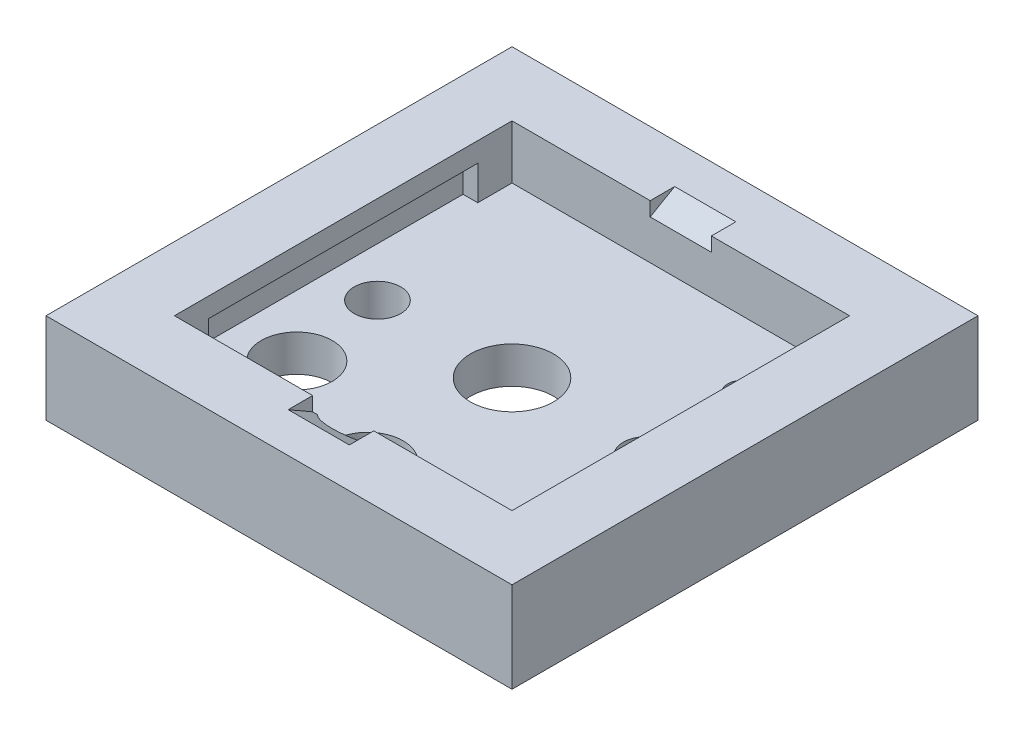
SolidWorks part; units mm, degrees
other "single-1350"
ref_plane "Front Plane" through (0, 0, 0) normal (0, 0, 1) x (1, 0, 0)
ref_plane "Top Plane" through (0, 0, 0) normal (0, 1, 0) x (1, 0, 0)
ref_plane "Right Plane" through (0, 0, 0) normal (1, 0, 0) x (0, 0, -1)
sketch "Sketch1" plane through (0, 0, 0) normal (0, 1, 0) x (1, 0, 0)
  line L0 (-6.9, 6.9) -> (6.9, 6.9)
  line L1 (6.9, 6.9) -> (6.9, -6.9)
  line L2 (6.9, -6.9) -> (1.05, -6.9)
  line L3 (-6.9, -6.9) -> (-6.9, 6.9)
  line L4 (13.0003, 0) -> (-13.0003, 0) construction
  line L5 (0, 13.0493) -> (0, -13.0493) construction
  line L6 (-1.05, -6.9) -> (-6.9, -6.9)
  line L8 (-9.525, -9.525) -> (9.525, -9.525)
  line L9 (-9.525, -9.525) -> (-9.525, 9.525)
  line L10 (-9.525, 9.525) -> (9.525, 9.525)
  line L11 (9.525, -9.525) -> (9.525, 9.525)
  line L12 (-9.525, -9.525) -> (9.525, 9.525) construction
  line L13 (-9.525, 9.525) -> (9.525, -9.525) construction
  circle A0 centre (0, 0) radius 1.7
  circle A1 centre (-5.5, 0) radius 0.95
  circle A2 centre (5.5, 0) radius 0.95
  circle A3 centre (-5, -3.8) radius 1.45
  circle A4 centre (0, -5.9) radius 1.45
  circle A5 centre (5.22, 4.2) radius 0.6
  point P20 (0, 0)
  point P23 (0, 0)
  dimension "D1" = 11
  dimension "D2" = 1.9
  dimension "D3" = 2.9
  dimension "D5" = 3.4
  dimension "D8" = 1.2
  dimension "D13" = 6.9
  dimension "D16" = 19.05
  dimension "D4" = 5
  dimension "D6" = 5.9
  dimension "D7" = 4.2
  dimension "D9" = 13.8
  dimension "D10" = 5.22
  dimension "D11" = 3.8
  dimension "D12" = 6.9
  dimension "D14" = 5.5
  dimension "D15" = 19.05
extrude "Boss-Extrude1" add sketch "Sketch1" along normal blind 3.7 contours L8 L11 L10 L9 A4 L6 L3 L0 L1 L2 | A4 L2 L1 L0 L3 L6 A5 A0 A1 A2 A3 region at (0, 0, -6.7048) region at (-9.2556, 0, 0)
extrude "Cut-Extrude1" cut sketch "Sketch1<3>" against normal blind 2.2 from surface contours A4 L2 L1 L0 L3 L6 A5 A0 A1 A2 A3 region at (0, 0, -6.7048) starting at face at (0, 3.7, 7.35)
sketch "Sketch1<3>" plane through (0, 0, 0) normal (0, 1, 0) x (1, 0, 0) same geometry as "Sketch1"
sketch "Sketch2" plane through (0, 0, 0) normal (1, 0, 0) x (0, 0, -1)
  line L0 (-7.9, 3.7) -> (-6.9, 3.7)
  line L1 (-6.9, 3.7) -> (-6.9, 3.1226)
  line L2 (-6.9, 3.1226) -> (-7.9, 3.7)
  line L3 (-6.9, 1.5) -> (-6.9, 3.7) construction
  dimension "D1" = 150
  dimension "D2" = 1
extrude "Cut-Extrude2" cut sketch "Sketch2" against normal mid plane 2.5
mirror "Mirror1" about plane through (0, 0, 0) normal (0, 0, 1) of "Cut-Extrude2"
sketch "Sketch4" plane through (0, 0, 0) normal (0, 0, 1) x (1, 0, 0)
  line L2 (-6.9, 2.9) -> (-6.9, 1.5)
  line L3 (-6.9, 1.5) -> (-7.5, 1.5)
  line L4 (-7.5, 2.8) -> (-7.5, 1.5)
  line L5 (-6.9, 3.7) -> (-7.5, 1.5) construction
  line L10 (-7.5, 2.8) -> (-7, 2.8)
  line L11 (-7, 2.8) -> (-6.9, 2.9)
  line L12 (-6.9, 3.7) -> (-6.9, 2.9) construction
  dimension "D1" = 0.9
  dimension "D2" = 0.6
  dimension "D4" = 45
  dimension "D5" = 0.5
extrude "Cut-Extrude3" cut sketch "Sketch4" against normal mid plane 11
mirror "Mirror2" about plane through (0, 0, 0) normal (1, 0, 0) of "Cut-Extrude3"
equation "\"key_spacing\"= 19.05mm"
